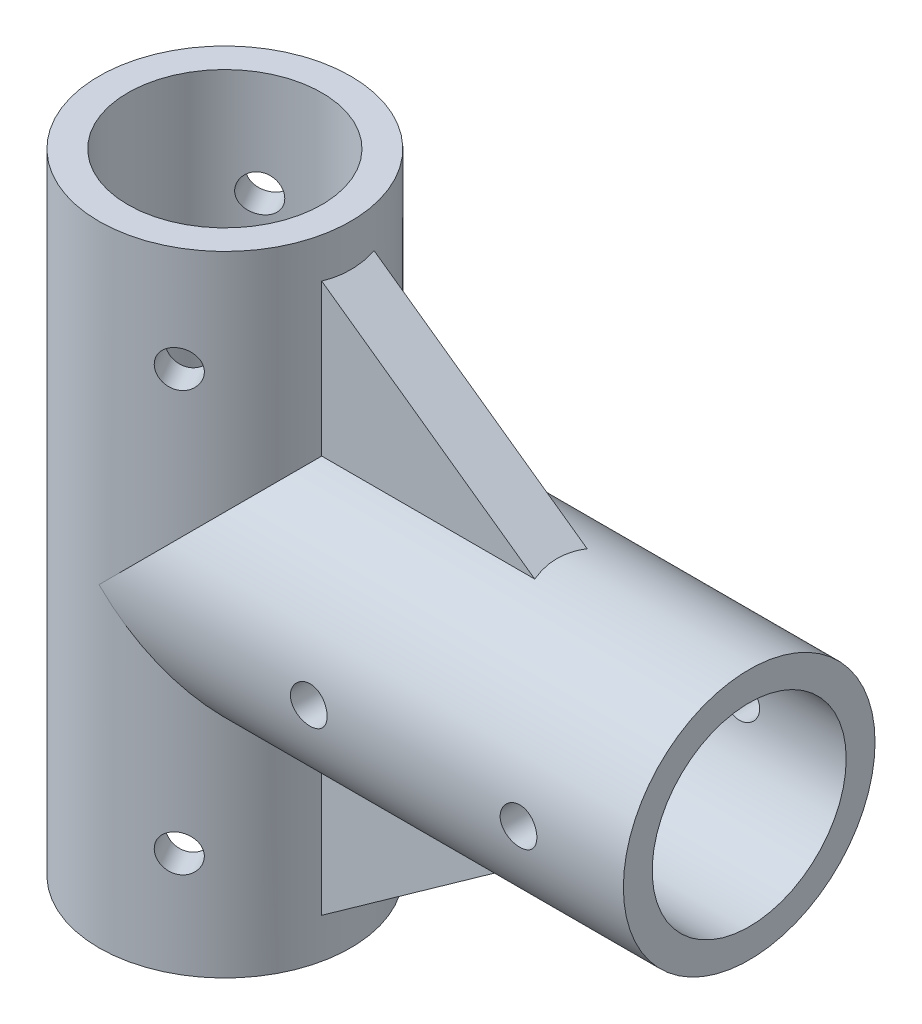
SolidWorks part; units mm, degrees
ref_plane "正面(Front)" through (0, 0, 0) normal (0, 0, 1) x (1, 0, 0)
ref_plane "平面(Top)" through (0, 0, 0) normal (0, 1, 0) x (1, 0, 0)
ref_plane "右側面(Right)" through (0, 0, 0) normal (1, 0, 0) x (0, 0, -1)
sketch "ｽｹｯﾁ1" plane through (0, 0, 0) normal (0, 1, 0) x (1, 0, 0)
  circle A0 centre (0, 0) radius 9.25
  circle A1 centre (0, 0) radius 12
  dimension "D1" = 18.5
  dimension "D2" = 24
extrude "ﾎﾞｽ - 押し出し1" add sketch "ｽｹｯﾁ1" along normal mid plane 60
sketch "ｽｹｯﾁ2" plane through (0, 0, 0) normal (1, 0, 0) x (0, 0, -1)
  circle A0 centre (0, 0) radius 9.25
  circle A1 centre (0, 0) radius 12
  dimension "D1" = 18.5
  dimension "D2" = 24
extrude "ﾎﾞｽ - 押し出し2" add sketch "ｽｹｯﾁ2" against normal up to next from offset 50
ref_axis "軸1" through (0, 33, 0) along (0, -1, 0)
ref_plane "平面1" through (0, 0, 0) normal (0.5, 0, 0.866) x (0, -1, 0)
sketch "ｽｹｯﾁ3" plane through (0, 0, 0) normal (0.5, 0, 0.866) x (0, -1, 0)
  line L0 (0, 0) -> (-31.6189, 0) construction
  line L1 (0, 0) -> (0, 58.6811) construction
  circle A0 centre (-20, 0) radius 1.75
  circle A1 centre (20, 0) radius 1.75
  dimension "D1" = 3.5
  dimension "D2" = 40
extrude "ｶｯﾄ - 押し出し1" cut sketch "ｽｹｯﾁ3" against normal through all both and the other way through all
sketch "ｽｹｯﾁ4" plane through (0, 0, 0) normal (0, 0, 1) x (1, 0, 0)
  line L0 (0, 0) -> (62.1172, 0) construction
  line L1 (50, -12) -> (50, 12) construction
  circle A0 centre (20, 0) radius 1.75
  circle A1 centre (40, 0) radius 1.75
  dimension "D1" = 10
  dimension "D2" = 20
  dimension "D3" = 3.5
extrude "ｶｯﾄ - 押し出し2" cut sketch "ｽｹｯﾁ4" against normal through all both and the other way through all
sketch "ｽｹｯﾁ5" plane through (0, 0, 0) normal (0, 0, 1) x (1, 0, 0)
  line L0 (10.4961, 27.0694) -> (33.2488, 10.8817)
  line L1 (33.2488, 10.8817) -> (10.4961, 10.4961)
  line L2 (0, 0) -> (12, 12) construction
  line L3 (10.4961, 10.4961) -> (10.4961, 27.0694)
  line L4 (0, 0) -> (56.7209, 0) construction
  line L5 (33.2488, -10.8817) -> (10.4961, -10.4961)
  line L6 (10.4961, -27.0694) -> (33.2488, -10.8817)
  line L7 (10.4961, -10.4961) -> (10.4961, -27.0694)
extrude "ﾎﾞｽ - 押し出し3" add sketch "ｽｹｯﾁ5" along normal mid plane 5
sketch "ｽｹｯﾁ6" plane through (50, 0, 0) normal (1, 0, 0) x (0, 0, -1)
  circle A0 centre (0, 0) radius 9.25 construction
  circle A1 centre (0, 0) radius 9.25
extrude "ｶｯﾄ - 押し出し3" cut sketch "ｽｹｯﾁ6" against normal up to surface (50 mm away) up to face at (-6.0269, 19.6322, -7.0171)
